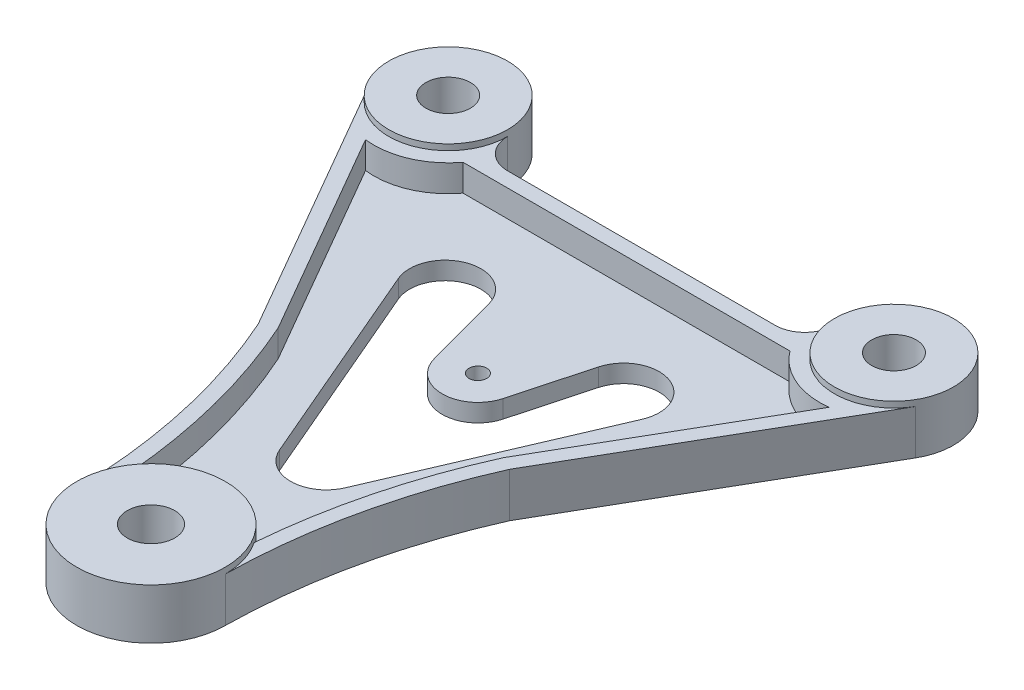
SolidWorks part; units mm, degrees
ref_plane "Front Plane" through (0, 0, 0) normal (0, 0, 1) x (1, 0, 0)
ref_plane "Top Plane" through (0, 0, 0) normal (0, 1, 0) x (1, 0, 0)
ref_plane "Right Plane" through (0, 0, 0) normal (1, 0, 0) x (0, 0, -1)
sketch "Sketch1" plane through (0, 0, 0) normal (0, 1, 0) x (1, 0, 0)
  line L1 (-77.9904, 150.1795) -> (-37.861, 80.6733)
  line L3 (0, 165) -> (45, 165)
  line L4 (92.3205, 165) -> (42.3205, 78.3975)
  line L5 (-55, 160) -> (55, 160)
  line L6 (11.0297, 54.273) -> (41.0297, 124.273)
  line L7 (11.5839, 106.8675) -> (18.4161, 132.1325)
  line L8 (0, 160) -> (45, 160) construction
  line L9 (77.9904, 150.1795) -> (37.861, 80.6733)
  line L10 (-11.5839, 106.8675) -> (-18.4161, 132.1325)
  line L11 (-11.0297, 54.273) -> (-41.0297, 124.273)
  line L12 (-92.3205, 165) -> (-42.3205, 78.3975)
  line L13 (0, 165) -> (-45, 165)
  circle A0 centre (0, 0) radius 8
  circle A1 centre (0, 0) radius 25
  circle A2 centre (75, 175) radius 20
  circle A3 centre (75, 175) radius 7.5
  arc A4 (-11.5839, 106.8675) -> (11.5839, 106.8675) centre (0, 110) ccw
  circle A5 centre (0, 110) radius 3
  arc A6 (41.0297, 124.273) -> (18.4161, 132.1325) centre (30, 129) ccw
  arc A7 (-11.0297, 54.273) -> (11.0297, 54.273) centre (0, 59) ccw
  arc A10 (45, 165) -> (55, 175) centre (45, 175) ccw
  arc A11 (25, 0) -> (42.3205, 78.3975) centre (224.9764, -3.0691) cw
  arc A12 (55, 160) -> (77.9904, 150.1795) centre (75, 175) ccw
  circle A13 centre (75, 175) radius 25 construction
  arc A14 (20.6909, 14.0316) -> (37.861, 80.6733) centre (224.9764, -3.0691) cw
  arc A15 (20.0006, 0.0767) -> (37.7541, 80.4341) centre (224.9764, -3.0691) cw construction
  arc A16 (-20.6909, 14.0316) -> (-37.861, 80.6733) centre (-224.9764, -3.0691) ccw
  arc A17 (-55, 160) -> (-77.9904, 150.1795) centre (-75, 175) cw
  arc A18 (-25, 0) -> (-42.3205, 78.3975) centre (-224.9764, -3.0691) ccw
  arc A19 (-45, 165) -> (-55, 175) centre (-45, 175) cw
  arc A20 (-41.0297, 124.273) -> (-18.4161, 132.1325) centre (-30, 129) cw
  circle A21 centre (-75, 175) radius 7.5
  circle A22 centre (-75, 175) radius 20
  circle A23 centre (0, 0) radius 25
  point P12 (0, 0)
  dimension "D1" = 5
  dimension "D2" = 5
extrude "Boss-Extrude1" add sketch "Sketch1" along normal blind 17 contours A22 A21 | A2 A3 | A1 A0 region at (0, 0, -24.2929) region at (-80.03, 0, -193.7721) region at (69.97, 0, -156.2279)
extrude "Boss-Extrude4" add sketch "Sketch1<11>" along normal blind 15 contours A19 A22 L12 A18 A1 A16 L1 A17 L5 A12 L9 A14 A11 L4 A2 A10 L3 L13 region at (-60.1288, 0, -114.1544)
sketch "Sketch1<11>" plane through (0, 0, 0) normal (0, 1, 0) x (1, 0, 0) same geometry as "Sketch1"
extrude "Boss-Extrude5" add sketch "Sketch1<12>" along normal blind 6 contours L5 A17 L1 A16 A1 A14 L9 A12 A5 L11 A20 L10 A4 L7 A6 L6 A7 region at (-64.3403, 0, -150.0451)
sketch "Sketch1<12>" plane through (0, 0, 0) normal (0, 1, 0) x (1, 0, 0) same geometry as "Sketch1"
sketch "Sketch2" plane through (0, 6, 0) normal (0, 1, 0) x (1, 0, 0)
  line L27 (69.5181, 145.5051) -> (33.403, 82.9519)
  line L28 (-33.403, 82.9519) -> (-69.5181, 145.5051)
  line L29 (-52.6393, 155) -> (52.6393, 155)
  line L30 (69.5181, 145.5051) -> (33.403, 82.9519)
  line L31 (-33.403, 82.9519) -> (-69.5181, 145.5051)
  line L32 (-52.6393, 155) -> (52.6393, 155)
  circle A28 centre (0, 0) radius 30
  arc A29 (16.8378, 24.8292) -> (-16.8378, 24.8292) centre (0, 0) ccw
  arc A30 (-15.7084, 14.4486) -> (-33.403, 82.9519) centre (-224.9764, -3.0691) ccw
  arc A31 (33.403, 82.9519) -> (15.7084, 14.4486) centre (224.9764, -3.0691) ccw
  arc A32 (52.6393, 155) -> (69.5181, 145.5051) centre (75, 175) ccw
  arc A33 (-69.5181, 145.5051) -> (-52.6393, 155) centre (-75, 175) ccw
  arc A34 (-16.8378, 24.8292) -> (-33.403, 82.9519) centre (-224.9764, -3.0691) ccw
  arc A35 (33.403, 82.9519) -> (16.8378, 24.8292) centre (224.9764, -3.0691) ccw
  arc A36 (52.6393, 155) -> (69.5181, 145.5051) centre (75, 175) ccw
  arc A37 (-69.5181, 145.5051) -> (-52.6393, 155) centre (-75, 175) ccw
  dimension "D1" = 5
  dimension "D2" = 5
sketch "Sketch3" plane through (0, 15, 0) normal (0, 1, 0) x (1, 0, 0)
  line L6 (37.861, 80.6733) -> (77.9904, 150.1795)
  line L7 (-77.9904, 150.1795) -> (-37.861, 80.6733)
  line L8 (55, 160) -> (-55, 160)
  line L9 (37.861, 80.6733) -> (77.9904, 150.1795)
  line L10 (-77.9904, 150.1795) -> (-37.861, 80.6733)
  line L11 (55, 160) -> (-55, 160)
  arc A10 (37.861, 80.6733) -> (20.6909, 14.0316) centre (224.9764, -3.0691) ccw
  arc A11 (20.6909, 14.0316) -> (-20.6909, 14.0316) centre (0, 0) ccw
  arc A12 (-20.6909, 14.0316) -> (-37.861, 80.6733) centre (-224.9764, -3.0691) ccw
  arc A13 (-77.9904, 150.1795) -> (-55, 160) centre (-75, 175) ccw
  arc A14 (55, 160) -> (77.9904, 150.1795) centre (75, 175) ccw
  arc A15 (37.861, 80.6733) -> (20.6909, 14.0316) centre (224.9764, -3.0691) ccw
  arc A16 (20.6909, 14.0316) -> (-20.6909, 14.0316) centre (0, 0) ccw
  arc A17 (-20.6909, 14.0316) -> (-37.861, 80.6733) centre (-224.9764, -3.0691) ccw
  arc A18 (-77.9904, 150.1795) -> (-55, 160) centre (-75, 175) ccw
  arc A19 (55, 160) -> (77.9904, 150.1795) centre (75, 175) ccw
  dimension "D1" = 5
